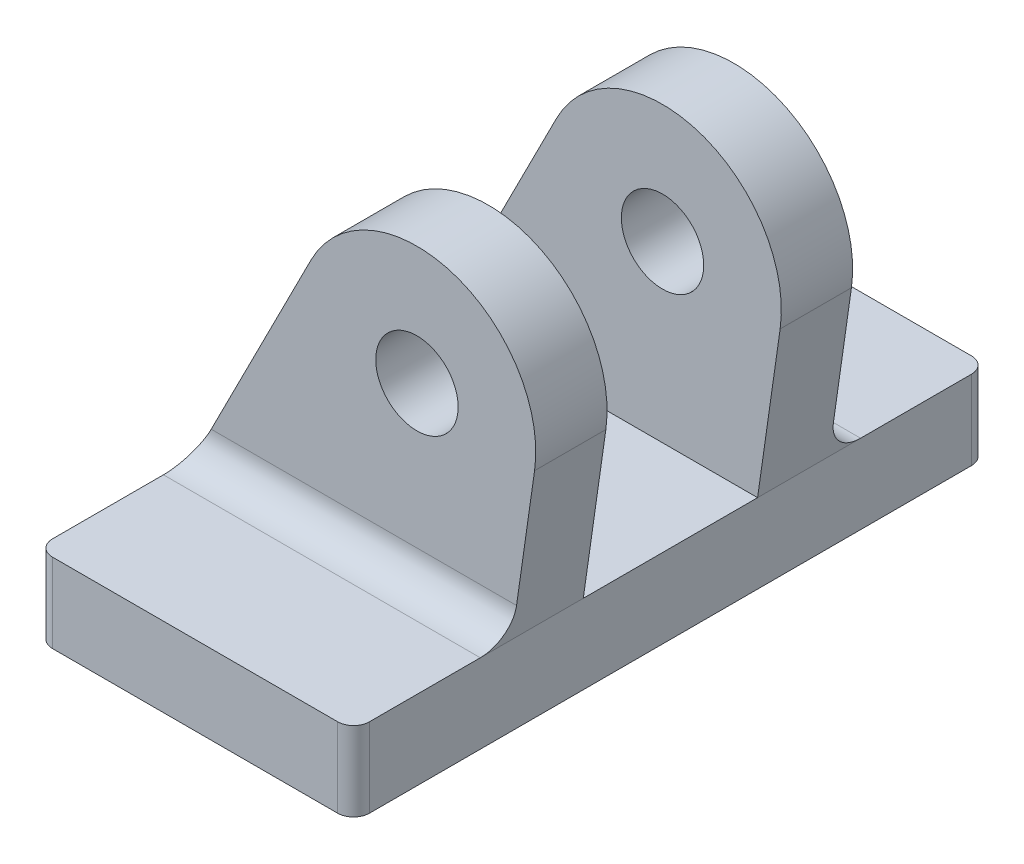
SolidWorks part; units mm, degrees
ref_plane "Front Plane" through (0, 0, 0) normal (0, 0, 1) x (1, 0, 0)
ref_plane "Top Plane" through (0, 0, 0) normal (0, 1, 0) x (1, 0, 0)
ref_plane "Right Plane" through (0, 0, 0) normal (1, 0, 0) x (0, 0, -1)
sketch "Sketch1" plane through (0, 0, 0) normal (0, 0, 1) x (1, 0, 0)
  line L1 (-2.6867, 19.3967) -> (-10, 5)
  line L2 (-10, 5) -> (-10, 0)
  line L3 (-10, 0) -> (10, 0)
  line L4 (10, 5) -> (10, 0)
  line L5 (11.4241, 14.9359) -> (10, 5)
  line L6 (-10, 5) -> (10, 5)
  circle A0 centre (4, 16) radius 2.6
  arc A1 (11.4241, 14.9359) -> (-2.6867, 19.3967) centre (4, 16) ccw
  point P10 (0, 0)
  dimension "D1" = 5.2
  dimension "D2" = 7.5
  dimension "D3" = 5
  dimension "D4" = 20
  dimension "D5" = 16
  dimension "D6" = 4
extrude "Boss-Extrude1" add sketch "Sketch1" along normal mid plane 20 contours A0 A1 L1 L6 L5 region at (2.2758, 12.8173, 0)
extrude "Boss-Extrude2" add sketch "Sketch1<3>" along normal mid plane 40 contours L6 L2 L3 L4 region at (0, 2.5, 0)
sketch "Sketch1<3>" plane through (0, 0, 0) normal (0, 0, 1) x (1, 0, 0) same geometry as "Sketch1"
extrude "Cut-Extrude1" cut sketch "Sketch1<4>" against normal mid plane 11 contours A0 A1 L1 L6 L5 region at (2.2758, 12.8173, 0)
sketch "Sketch1<4>" plane through (0, 0, 0) normal (0, 0, 1) x (1, 0, 0) same geometry as "Sketch1"
sketch "Sketch2" plane through (0, 0, 0) normal (0, -1, 0) x (1, 0, 0)
  line L0 (-14.2709, 0) -> (31.1543, 0) construction
  circle A0 centre (0, 10) radius 2
  circle A1 centre (0, -10) radius 2
  point P7 (0, 0)
  dimension "D1" = 4
  dimension "D2" = 20
extrude "Boss-Extrude3" add sketch "Sketch2" along normal blind 4
fillet "Fillet1" radius 1 4 edges at (-10, 2.5, -20) (10, 2.5, -20) (-10, 2.5, 20) (10, 2.5, 20)
fillet "Fillet2" radius 2 2 edges at (0, 5, -10) (0, 5, 10)
